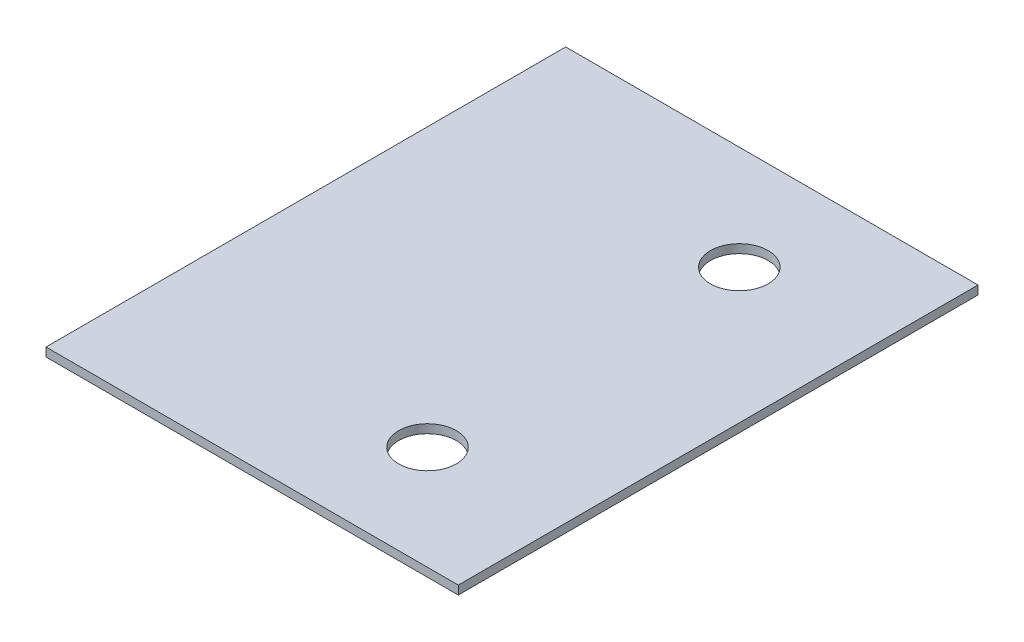
SolidWorks part; units mm, degrees
ref_plane "Front" through (0, 0, 0) normal (0, 0, 1) x (1, 0, 0)
ref_plane "Top" through (0, 0, 0) normal (0, 1, 0) x (1, 0, 0)
ref_plane "Right" through (0, 0, 0) normal (1, 0, 0) x (0, 0, -1)
sketch "Sketch1" plane through (0, 0, 0) normal (0, 1, 0) x (1, 0, 0)
  line L1 (-11.9, 15) -> (11.9, 15)
  line L2 (-11.9, 15) -> (-11.9, -15)
  line L3 (-11.9, -15) -> (11.9, -15)
  line L4 (11.9, 15) -> (11.9, -15)
  line L5 (-11.9, 15) -> (11.9, -15) construction
  line L6 (-11.9, -15) -> (11.9, 15) construction
  point P0 (0, 0)
  dimension "D1" = 23.8
  dimension "D2" = 30
extrude "Boss-Extrude1" add sketch "Sketch1" along normal blind 0.5
sketch "Sketch2" plane through (0, 0.5, 0) normal (0, 1, 0) x (1, 0, 0)
  line L0 (11.9, -15) -> (11.9, 15) construction
  line L1 (4.1214, -9) -> (4.1214, -15) construction
  line L2 (-11.9, -15) -> (11.9, -15) construction
  line L3 (4.1214, 9) -> (4.1214, 15) construction
  line L4 (11.9, 15) -> (-11.9, 15) construction
  line L5 (4.1214, -9) -> (4.1214, 9) construction
  circle A0 centre (4.1214, 9) radius 1.665
  circle A1 centre (4.1214, -9) radius 1.665
  dimension "D1" = 3.33
  dimension "D2" = 7.7786
  dimension "D3" = 18
extrude "Cut-Extrude1" cut sketch "Sketch2" against normal up to next
